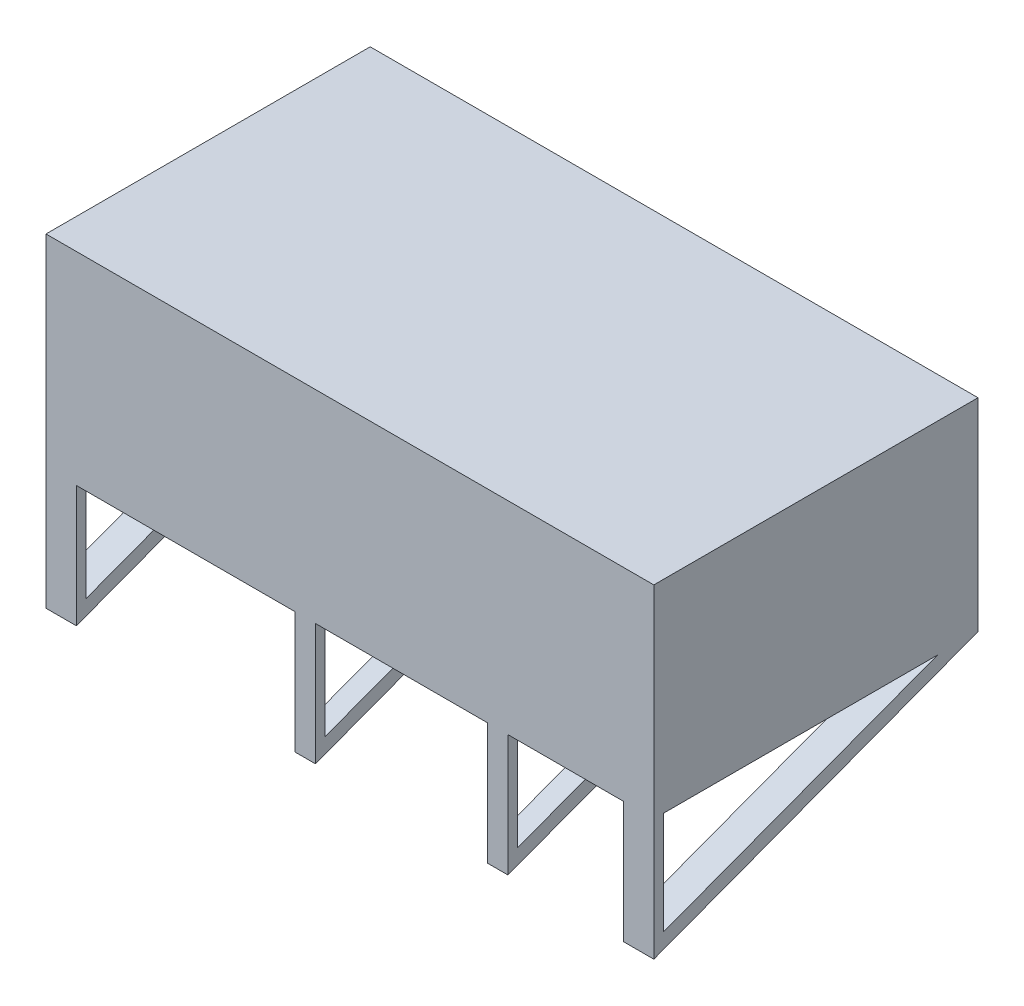
SolidWorks part; units mm, degrees
ref_plane "Front Plane" through (0, 0, 0) normal (0, 0, 1) x (1, 0, 0)
ref_plane "Top Plane" through (0, 0, 0) normal (0, 1, 0) x (1, 0, 0)
ref_plane "Right Plane" through (0, 0, 0) normal (1, 0, 0) x (0, 0, -1)
sketch "LeftSideSketch" plane through (0, 0, 0) normal (1, 0, 0) x (0, 0, -1)
  line L0 (0, 0) -> (160, 0)
  line L1 (160, 0) -> (160, -100)
  line L3 (0, -100) -> (0, 0)
  line L5 (5, -5) -> (5, -95)
  line L6 (5, -95) -> (155, -95)
  line L7 (155, -95) -> (155, -5)
  line L9 (5, -5) -> (155, -5)
  line L10 (0, -100) -> (0, -160)
  line L11 (0, -160) -> (160, -100)
  line L12 (4.8121, -100) -> (4.8121, -150.7195)
  line L13 (4.8121, -150.7195) -> (140.064, -100)
  line L15 (0, -100) -> (4.8121, -100)
  line L16 (4.8121, -100) -> (140.064, -100)
  line L17 (140.064, -100) -> (160, -100)
  dimension "D1" = 160
  dimension "D2" = 100
  dimension "D3" = 5
  dimension "D4" = 5
  dimension "D5" = 5
  dimension "D6" = 5
  dimension "D7" = 7
  dimension "D8" = 4.8121
  dimension "D10" = 60
extrude "walls" add sketch "LeftSideSketch" along normal blind 300 contours L3 L1 L0 L5 L9 L7 L6 region at (0, -1.8868, -80)
extrude "leg1" add sketch "LeftSideSketch<4>" along normal blind 15 contours L10 L11 L13 L12 region at (0, -101.7088, -2.406)
sketch "LeftSideSketch<4>" plane through (0, 0, 0) normal (1, 0, 0) x (0, 0, -1) same geometry as "LeftSideSketch"
extrude "leg4" add sketch "LeftSideSketch<5>" against normal blind 15 from surface contours L10 L11 L13 L12 region at (0, -101.7088, -2.406) starting at face at (300, -50, -80)
sketch "LeftSideSketch<5>" plane through (0, 0, 0) normal (1, 0, 0) x (0, 0, -1) same geometry as "LeftSideSketch"
ref_plane "refPlane1" through (123, 0, 0) normal (1, 0, 0) x (0, 0, -1)
ref_plane "refPlane2" through (223, 0, 0) normal (1, 0, 0) x (0, 0, -1)
extrude "leg2" add sketch "LeftSideSketch<7>" along normal blind 10 from surface contours L17 L13 L12 L15 L10 L11 region at (0, -101.7088, -2.406) starting at plane "refPlane1"
sketch "LeftSideSketch<7>" plane through (0, 0, 0) normal (1, 0, 0) x (0, 0, -1) same geometry as "LeftSideSketch"
extrude "leg3" add sketch "LeftSideSketch<9>" along normal mid plane 10 from surface contours L17 L13 L12 L15 L10 L11 region at (0, -101.7088, -2.406) starting at plane "refPlane2"
sketch "LeftSideSketch<9>" plane through (0, 0, 0) normal (1, 0, 0) x (0, 0, -1) same geometry as "LeftSideSketch"
extrude "right wall" add sketch "LeftSideSketch<10>" along normal blind 5 contours L9 L5 L6 L7 region at (0, -50, -80)
sketch "LeftSideSketch<10>" plane through (0, 0, 0) normal (1, 0, 0) x (0, 0, -1) same geometry as "LeftSideSketch"
extrude "left wall" add sketch "LeftSideSketch<11>" against normal blind 5 from surface contours L9 L5 L6 L7 region at (0, -50, -80) starting at face at (300, -116.9065, -49.896)
sketch "LeftSideSketch<11>" plane through (0, 0, 0) normal (1, 0, 0) x (0, 0, -1) same geometry as "LeftSideSketch"
sketch "TableSketch" plane through (0, -95, 0) normal (0, 1, 0) x (1, 0, 0)
  line L0 (40, 112.5) -> (40, 47.5)
  line L1 (40, 47.5) -> (200, 47.5)
  line L2 (200, 47.5) -> (200, 112.5)
  line L3 (40, 112.5) -> (200, 112.5)
  line L4 (177.75, 112.5) -> (177.75, 101.25)
  line L5 (177.75, 101.25) -> (190, 101.25)
  line L6 (190, 101.25) -> (190, 58.75)
  line L7 (190, 58.75) -> (147.5, 58.75)
  line L8 (147.5, 58.75) -> (147.5, 101.25)
  line L9 (147.5, 101.25) -> (159.75, 101.25)
  line L10 (159.75, 101.25) -> (159.75, 112.5)
  line L11 (295, 5) -> (5, 5) construction
  line L12 (200, 47.5) -> (137.5, 47.5)
  line L13 (200, 47.5) -> (200, 112.5)
  line L14 (200, 112.5) -> (137.5, 112.5)
  line L15 (137.5, 47.5) -> (137.5, 112.5)
  line L18 (295, 155) -> (295, 5) construction
  circle A0 centre (78.75, 80) radius 27
  circle A1 centre (78.75, 80) radius 19.2
  circle A6 centre (78.75, 53) radius 3
  circle A7 centre (61.3947, 59.3168) radius 3
  circle A8 centre (52.1602, 75.3115) radius 3
  circle A9 centre (55.3673, 93.5) radius 3 [skipped]
  circle A10 centre (69.5155, 105.3717) radius 3 [skipped]
  circle A11 centre (87.9845, 105.3717) radius 3 [skipped]
  circle A12 centre (102.1327, 93.5) radius 3 [skipped]
  circle A13 centre (105.3398, 75.3115) radius 3
  circle A14 centre (96.1053, 59.3168) radius 3
  circle A15 centre (78.75, 80) radius 30
  circle A16 centre (78.75, 80) radius 24
  point P17 (168.75, 80)
  point P20 (147.5, 80)
  point P44 (78.75, 80)
  dimension "D7" = 38.4
  dimension "D13" = 54
  dimension "D14" = 9
  dimension "D15" = 95
  dimension "D17" = 32.5
  dimension "D18" = 6
  dimension "D19" = 12.1602
  dimension "D20" = 27.8115
  dimension "D1" = 160
  dimension "D2" = 65
  dimension "D3" = 18
  dimension "D4" = 42.5
  dimension "D5" = 12.25
  dimension "D6" = 11.25
  dimension "D8" = 10
  dimension "D9" = 10
  dimension "D10" = 21.25
  dimension "D11" = 21.25
  dimension "D12" = 90
  dimension "D16" = 75
extrude "motor holder" add sketch "TableSketch" against normal blind 33 contours L15 L1 L2 L3 L4 L5 L6 L7 L8 L9 L10 | L13 L12 L15 L14 region at (148.625, -95, -111.5983)
extrude "motor holder2" cut sketch "TableSketch<5>" against normal blind 20.5 contours L10 L9 L8 L7 L6 L5 L4 L3 region at (168.75, -95, -82.7092)
sketch "TableSketch<5>" plane through (0, -95, 0) normal (0, 1, 0) x (1, 0, 0) same geometry as "TableSketch"
extrude "bearing cut" cut sketch "TableSketch<7>" against normal blind 1.74 contours A0 A7 | A0 A8 | A0 A6 | A0 A13 | A1 | A0 region at (104.0568, -95, -75.5377) region at (78.75, -95, -54.3028) region at (62.2322, -95, -60.3148) region at (53.4432, -95, -75.5377) region at (78.75, -95, -80)
sketch "TableSketch<7>" plane through (0, -95, 0) normal (0, 1, 0) x (1, 0, 0) same geometry as "TableSketch"
extrude "carousel hole" cut sketch "TableSketch<14>" against normal blind 5 contours A1 region at (78.75, -95, -80)
sketch "TableSketch<14>" plane through (0, -95, 0) normal (0, 1, 0) x (1, 0, 0) same geometry as "TableSketch"
extrude "Boss-Extrude10" add sketch "TableSketch<8>" against normal blind 15 from surface contours A0 A14 | A0 A14 | A0 A13 | A0 A13 | A0 A6 | A0 A6 | A0 A7 | A0 A7 | A0 A8 | A0 A8 region at (106.5637, -95, -75.0957) region at (104.0568, -95, -75.5377) region at (96.9041, -95, -58.3648) region at (95.2678, -95, -60.3148) region at (78.75, -95, -54.3028) region at (78.75, -95, -51.7573) region at (62.2322, -95, -60.3148) region at (53.4432, -95, -75.5377) region at (60.5959, -95, -58.3648) region at (50.9363, -95, -75.0957) starting at face at (78.75, -100, -60.8)
sketch "TableSketch<8>" plane through (0, -95, 0) normal (0, 1, 0) x (1, 0, 0) same geometry as "TableSketch"
extrude "funnel top" add sketch "TableSketch<9>" against normal blind 2 from surface contours A16 | A15 starting at face at (96.1053, -115, -56.3168)
sketch "TableSketch<9>" plane through (0, -95, 0) normal (0, 1, 0) x (1, 0, 0) same geometry as "TableSketch"
ref_plane "Funnel Plane (!!)" through (0, 0, -80) normal (0, 0, 1) x (1, 0, 0)
sketch "Sketch4" plane through (0, 0, -80) normal (0, 0, 1) x (1, 0, 0)
  line L1 (54.75, -117) -> (102.75, -117) construction
  line L6 (78.75, -1138.7657) -> (78.75, 48861.2343) construction
  line L7 (48.75, -117) -> (75.57, -137)
  line L8 (48.75, -115) -> (48.75, -117) construction
  line L9 (75.57, -137) -> (77.06, -137)
  line L10 (77.06, -137) -> (54.6993, -117)
  line L11 (54.6993, -117) -> (48.75, -117)
  line L13 (48.75, -117) -> (108.75, -117) construction
  dimension "D1" = 0
  dimension "D2" = 1.69
  dimension "D3" = 1.49
  dimension "D4" = 20
  dimension "D5" = 30
revolve "funnel revolve" add sketch "Sketch4" angle 360 about L6
sketch "Sketch5" plane through (0, -5, 0) normal (0, -1, 0) x (1, 0, 0)
  line L0 (295, -107.5) -> (295, -52.5)
  line L1 (295, -52.5) -> (55, -52.5)
  line L2 (55, -52.5) -> (55, -107.5)
  line L3 (55, -107.5) -> (295, -107.5)
  line L4 (115, -52.5) -> (115, -107.5)
  line L5 (295, -155) -> (5, -155) construction
  line L7 (295, -155) -> (295, -5) construction
  line L8 (165, -59.75) -> (165, -100.25)
  line L9 (165, -100.25) -> (190, -100.25)
  line L10 (235.25, -100.25) -> (235.25, -59.75)
  line L11 (235.25, -59.75) -> (210.25, -59.75)
  line L12 (250.5, -59.75) -> (250.5, -100.25)
  line L13 (250.5, -100.25) -> (275.5, -100.25)
  line L14 (275.5, -100.25) -> (275.5, -59.75)
  line L15 (275.5, -59.75) -> (250.5, -59.75)
  line L16 (190, -59.75) -> (190, -100.25)
  line L17 (210.25, -59.75) -> (210.25, -100.25)
  line L18 (210.25, -100.25) -> (235.25, -100.25)
  line L19 (190, -59.75) -> (165, -59.75)
  point P6 (115, -80)
  point P23 (165, -80)
  dimension "D1" = 55
  dimension "D2" = 240
  dimension "D3" = 60
  dimension "D4" = 47.5
  dimension "D5" = 0
  dimension "D6" = 40.5
  dimension "D7" = 7.25
  dimension "D8" = 25
  dimension "D9" = 25
  dimension "D10" = 50
  dimension "D11" = 70.25
  dimension "D12" = 25
  dimension "D13" = 15.25
  dimension "D14" = 40.5
  dimension "D15" = 7.25
extrude "spectrophotometer holder" add sketch "Sketch5" along normal blind 59.48 contours L16 L19 L8 L9 | L17 L18 L10 L11 region at (177.5, -5, -80) region at (222.75, -5, -80)
extrude "zoom lense holder" add sketch "Sketch5<3>" along normal blind 59.3 contours L14 L15 L12 L13 region at (263, -5, -80)
sketch "Sketch5<3>" plane through (0, -5, 0) normal (0, -1, 0) x (1, 0, 0) same geometry as "Sketch5"
fillet "holder fillets" radius 10 6 edges at (177.5, -64.48, -100.25) (222.75, -64.48, -100.25) (263, -64.3, -100.25) (263, -64.3, -59.75) (222.75, -64.48, -59.75) (177.5, -64.48, -59.75)
sketch "Sketch7" plane through (275.5, 0, 0) normal (1, 0, 0) x (0, 0, -1)
  line L1 (90.25, -64.3) -> (69.75, -64.3) construction
  line L3 (100.25, -5) -> (59.75, -5) construction
  line L4 (85.25, -5) -> (100.25, -30)
  line L5 (100.25, -54.3) -> (100.25, -5) construction
  line L6 (100.25, -30) -> (100.25, -5)
  line L7 (100.25, -5) -> (85.25, -5)
  line L8 (74.75, -5) -> (59.75, -5)
  line L9 (59.75, -5) -> (59.75, -30)
  line L10 (59.75, -54.3) -> (59.75, -5) construction
  line L11 (59.75, -30) -> (74.75, -5)
  circle A0 centre (79.4214, -46.9) radius 14
  dimension "D1" = 28
  dimension "D2" = 17.4
  dimension "D3" = 25
  dimension "D4" = 15
extrude "zoom lense cut" cut sketch "Sketch7" against normal blind 25 contours A0 | L8 L9 L11 | L4 L6 L7
sketch "Sketch8" plane through (235.25, 0, 0) normal (1, 0, 0) x (0, 0, -1)
  line L0 (90.25, -64.48) -> (69.75, -64.48) construction
  line L1 (74.75, -5) -> (59.75, -5)
  line L2 (100.25, -5) -> (59.75, -5) construction
  line L3 (59.75, -5) -> (59.75, -30)
  line L4 (59.75, -54.48) -> (59.75, -5) construction
  line L5 (59.75, -30) -> (74.75, -5)
  line L6 (85.25, -5) -> (100.25, -5)
  line L7 (100.25, -5) -> (100.25, -30)
  line L8 (100.25, -54.48) -> (100.25, -5) construction
  line L9 (100.25, -30) -> (85.25, -5)
  circle A0 centre (80.3907, -46.99) radius 12.5
  dimension "D1" = 25
  dimension "D2" = 17.49
  dimension "D3" = 15
  dimension "D4" = 25
extrude "spectrophotometer cut" cut sketch "Sketch8" against normal blind 90
fillet "holder fillets1" radius 10 6 edges at (263, -30, -100.25) (222.75, -30, -100.25) (177.5, -30, -100.25) (263, -30, -59.75) (222.75, -30, -59.75) (177.5, -30, -59.75)
fillet "top holder fillets" radius 5 6 edges at (263, -5, -74.75) (222.75, -5, -74.75) (177.5, -5, -74.75) (222.75, -5, -85.25) (177.5, -5, -85.25) (263, -5, -85.25)
